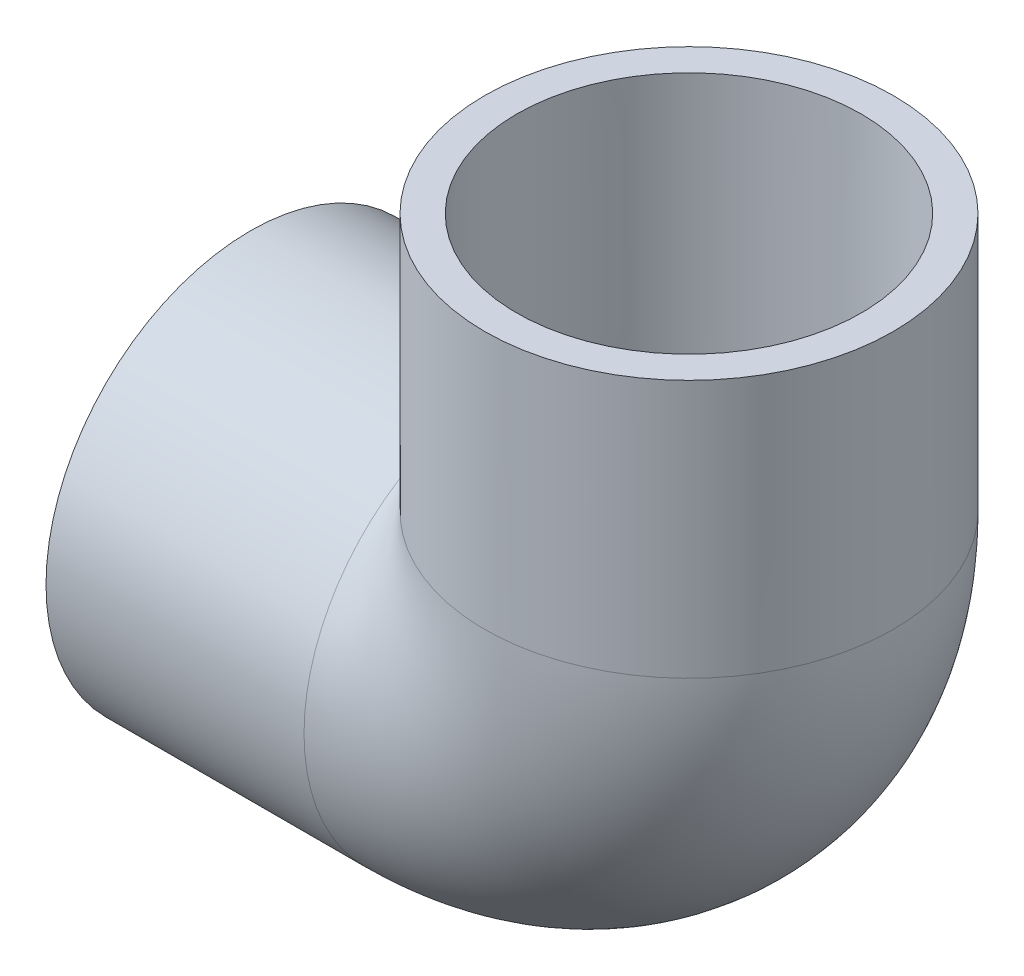
SolidWorks part; units mm, degrees
ref_plane "Front Plane" through (0, 0, 0) normal (0, 0, 1) x (1, 0, 0)
ref_plane "Top Plane" through (0, 0, 0) normal (0, 1, 0) x (1, 0, 0)
ref_plane "Right Plane" through (0, 0, 0) normal (1, 0, 0) x (0, 0, -1)
sketch "Sketch0" plane through (0, 0, 0) normal (0, 0, 1) x (1, 0, 0)
  line L0 (-53.975, 0) -> (0, 0) construction
  line L1 (0, 0) -> (0, 53.975) construction
  line L2 (-22.225, 0) -> (0, 0) construction
  line L3 (0, 0) -> (0, 22.225) construction
  line L4 (-53.975, 25.146) -> (-53.975, -25.146) construction
  line L5 (-22.225, 21.0185) -> (-53.975, 21.209) construction
  line L6 (-22.225, 21.0185) -> (-22.225, -21.0185) construction
  line L7 (-22.225, -21.0185) -> (-53.975, -21.209) construction
  line L8 (-53.975, 21.209) -> (-53.975, -21.209) construction
  line L9 (-25.146, 53.975) -> (25.146, 53.975) construction
  line L10 (-21.209, 53.975) -> (21.209, 53.975) construction
  line L11 (21.209, 53.975) -> (21.0185, 22.225) construction
  line L12 (21.0185, 22.225) -> (-21.0185, 22.225) construction
  line L13 (-21.0185, 22.225) -> (-21.209, 53.975) construction
  line L14 (-22.225, 17.526) -> (-22.225, -17.526) construction
  line L18 (-17.526, 22.225) -> (17.526, 22.225) construction
  dimension "H" = 53.975
  dimension "G" = 22.225
  dimension "M" = 50.292
  dimension "OD A" = 42.418
  dimension "OD B" = 42.037
  dimension "ID" = 35.052
sketch "Sketch1" plane through (0, 0, 0) normal (0, 0, 1) x (1, 0, 0)
  line L0 (-53.975, 0) -> (0, 0) construction
  line L1 (-53.975, 0) -> (0, 0) construction
  line L3 (-53.975, -25.146) -> (-22.225, -25.146)
  line L4 (-53.975, -25.146) -> (-53.975, -21.209)
  line L5 (-53.975, -21.209) -> (-22.225, -21.0185)
  line L6 (-22.225, -25.146) -> (-22.225, -21.0185)
revolve "Revolve1" add sketch "Sketch1" angle 360 about L1
sketch "Sketch2" plane through (0, 0, 0) normal (0, 0, 1) x (1, 0, 0)
  line L0 (21.209, 53.975) -> (21.0185, 22.225)
  line L1 (21.0185, 22.225) -> (25.146, 22.225)
  line L2 (25.146, 22.225) -> (25.146, 53.975)
  line L3 (25.146, 53.975) -> (21.209, 53.975)
  line L4 (0, 0) -> (0, 53.975) construction
  line L5 (0, 0) -> (0, 53.975) construction
revolve "Revolve2" add sketch "Sketch2" angle 360 about L5
sketch "Sketch3" plane through (-22.225, 0, 0) normal (1, 0, 0) x (0, 0, -1)
  circle A0 centre (0, 0) radius 17.526
  circle A1 centre (0, 0) radius 25.146
sketch "Sketch4" plane through (0, 0, 0) normal (0, 0, 1) x (1, 0, 0)
  line L0 (-53.975, 0) -> (0, 0) construction
  line L1 (0, 0) -> (0, 53.975) construction
  line L2 (-53.975, 0) -> (-22.225, 0) construction
  line L3 (0, 22.225) -> (0, 53.975) construction
  arc A0 (-22.225, 0) -> (0, 22.225) centre (-22.225, 22.225) ccw
sweep "Sweep1" add profiles "Sketch3" path "Sketch4"
